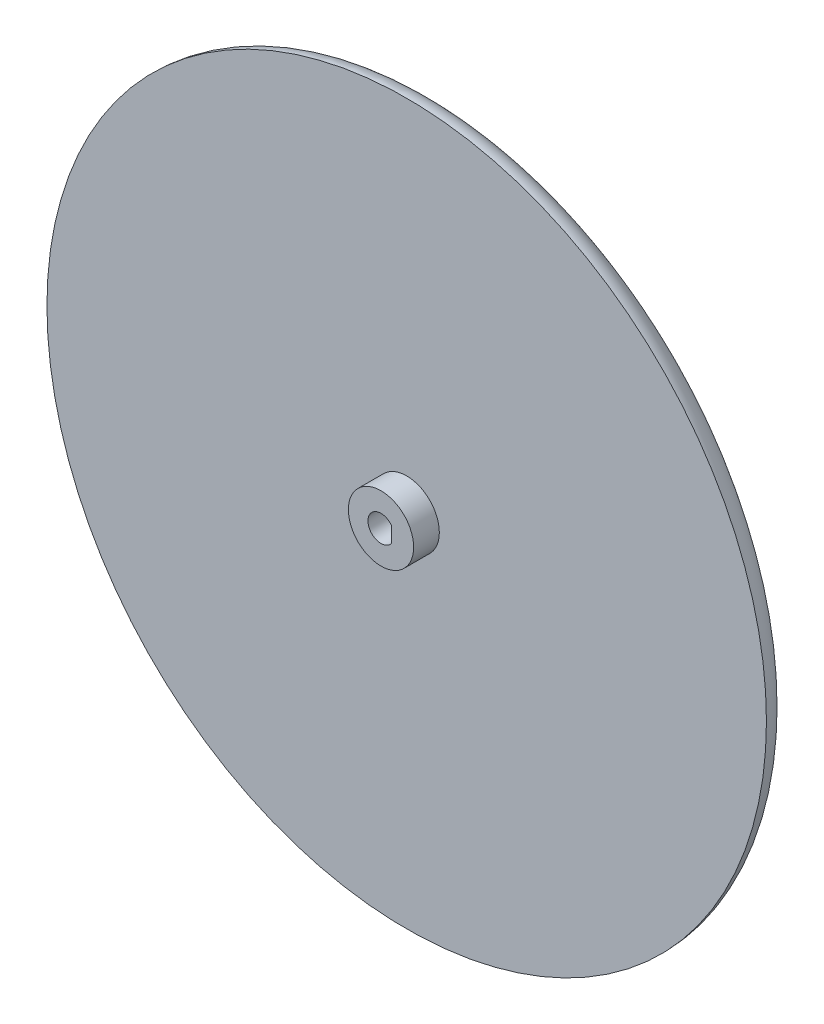
SolidWorks part; units mm, degrees
ref_plane "Front Plane" through (0, 0, 0) normal (0, 0, 1) x (1, 0, 0)
ref_plane "Top Plane" through (0, 0, 0) normal (0, 1, 0) x (1, 0, 0)
ref_plane "Right Plane" through (0, 0, 0) normal (1, 0, 0) x (0, 0, -1)
sketch "Sketch3" plane through (0, 0, 0) normal (0, 0, 1) x (1, 0, 0)
  circle A0 centre (0, 0) radius 6.35
  dimension "D1" = 12.7
extrude "Boss-Extrude2" add sketch "Sketch3" along normal blind 10 contours A0
sketch "Sketch4" plane through (0, 0, 10) normal (0, 0, 1) x (1, 0, 0)
  line L0 (2.042, -1.5105) -> (2.042, 1.5105)
  arc A0 (2.042, 1.5105) -> (2.042, -1.5105) centre (0, 0) ccw
  dimension "D1" = 2.54
  dimension "D2" = 3.0211
extrude "Cut-Extrude2" cut sketch "Sketch4" against normal blind 10
sketch "Sketch5" plane through (0, 0, 0) normal (0, 0, 1) x (1, 0, 0)
  circle A0 centre (0, 0) radius 70
  dimension "D1" = 140
extrude "Boss-Extrude3" add sketch "Sketch5" along normal blind 5
fillet "Fillet1" radius 5 1 edges at (70, 0, 0)
